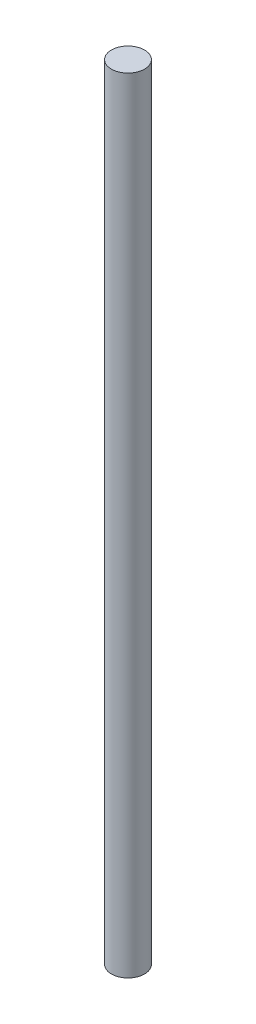
SolidWorks part; units mm, degrees
ref_plane "Front Plane" through (0, 0, 0) normal (0, 0, 1) x (1, 0, 0)
ref_plane "Top Plane" through (0, 0, 0) normal (0, 1, 0) x (1, 0, 0)
ref_plane "Right Plane" through (0, 0, 0) normal (1, 0, 0) x (0, 0, -1)
sketch "Sketch1" plane through (0, 0, 0) normal (0, 1, 0) x (1, 0, 0)
  circle A0 centre (0, 0) radius 4.7625
  dimension "D1" = 9.525
extrude "Boss-Extrude1" add sketch "Sketch1" along normal blind 225
